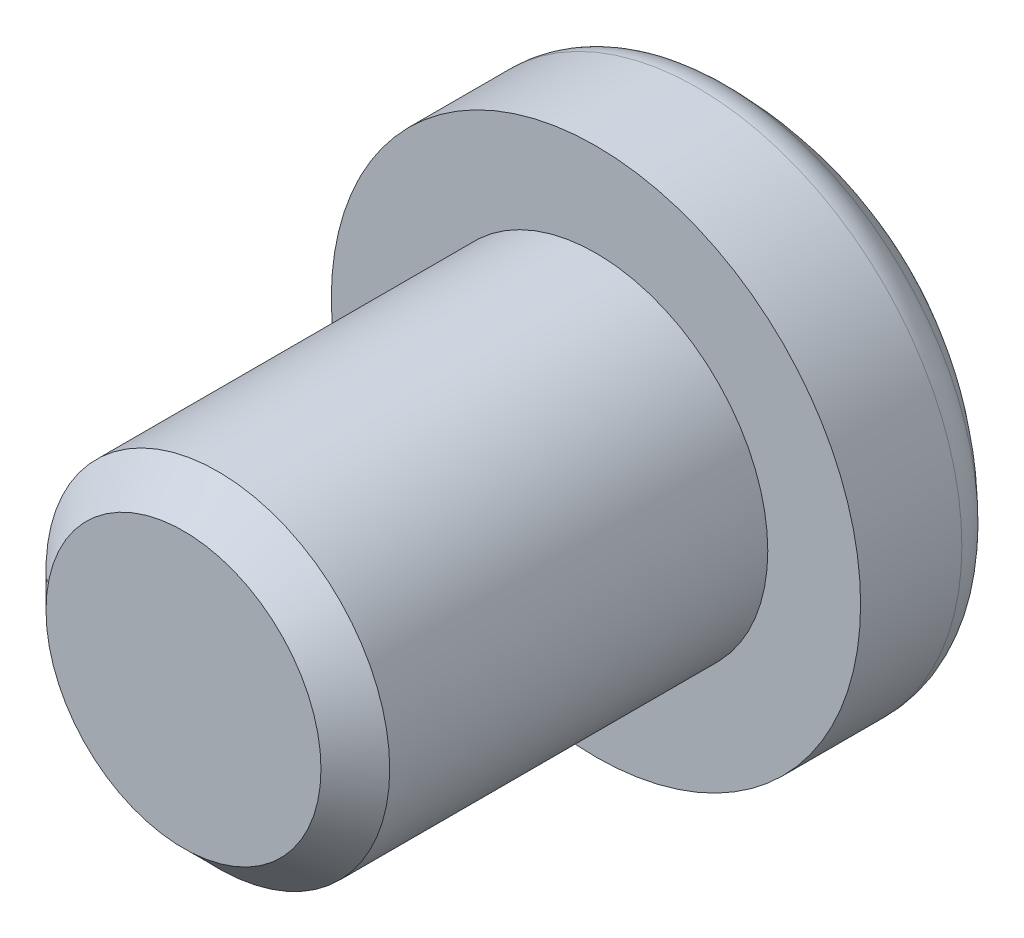
SolidWorks part; units mm, degrees
ref_plane "Plan1" through (0, 0, 0) normal (0, 0, 1) x (1, 0, 0)
ref_plane "Plan2" through (0, 0, 0) normal (0, 1, 0) x (1, 0, 0)
ref_plane "Plan3" through (0, 0, 0) normal (1, 0, 0) x (0, 0, -1)
ref_axis "Z Axis" through (0, 0, -50) along (0, 0, 1)
sketch "Esquisse1" plane through (0, 0, 0) normal (0, 1, 0) x (1, 0, 0)
  line L0 (0, 0) -> (0, 3.4) construction
  line L1 (0, 0) -> (3.85, 0)
  line L2 (0, 0) -> (0, 3.4)
  line L3 (0, 0) -> (0, 3.4) construction
  line L5 (3.85, 0) -> (3.85, 3.4) construction
  line L6 (3.85, 1.4731) -> (3.85, 0)
  arc A0 (0, 3.4) -> (3.6841, 1.8738) centre (0, -1.8096) cw
  arc A1 (3.6841, 1.8738) -> (3.85, 1.4731) centre (3.2833, 1.4731) cw
  point P9 (3.85, 1.7)
  dimension "D3" = 3.85
  dimension "D1" = 0.5667
  dimension "D2" = 3.4
revolve "Base-Révolution" add sketch "Esquisse1" angle 360 about L0 reverse direction yes
ref_plane "Plan4" through (0, 0, -3.4) normal (0, 0, 1) x (1, 0, 0)
sketch "Esquisse2" plane through (0, 0, -3.4) normal (0, 0, 1) x (1, 0, 0)
  line L0 (0.6, -0.6) -> (0.6, -2.35)
  line L1 (-2.35, 0.6) -> (-0.6, 0.6)
  line L2 (-2.35, 0.6) -> (-2.35, -0.6)
  line L3 (-2.35, -0.6) -> (-0.6, -0.6)
  line L4 (2.35, 0.6) -> (2.35, -0.6)
  line L5 (-0.6, 2.35) -> (0.6, 2.35)
  line L6 (-0.6, 2.35) -> (-0.6, 0.6)
  line L7 (-0.6, -2.35) -> (0.6, -2.35)
  line L8 (0.6, 2.35) -> (0.6, 0.6)
  line L9 (0.6, 0.6) -> (2.35, 0.6)
  line L10 (-0.6, -0.6) -> (-0.6, -2.35)
  line L11 (0.6, -0.6) -> (2.35, -0.6)
  dimension "D2" = 4.7
  dimension "D3" = 2.35
  dimension "D4" = 2.35
  dimension "D5" = 4.7
extrude "Enlev. mat.-Extru.1" cut sketch "Esquisse2" along normal blind 1.2
sketch "Esquisse3" plane through (0, 0, 0) normal (0, 1, 0) x (1, 0, 0)
  line L1 (0, 0) -> (0, -6) construction
  line L2 (0, 0) -> (2.5, 0)
  line L3 (0, 0) -> (0, -6)
  line L4 (0, -6) -> (2.5, -6)
  line L6 (2.5, 0) -> (2.5, -6)
  dimension "D1" = 6
  dimension "D2" = 2.5
revolve "Boss.-Révol.1" add sketch "Esquisse3" angle 360 about L1 reverse direction yes
sketch "Esquisse4" plane through (0, 0, 0) normal (0, 1, 0) x (1, 0, 0)
  line L0 (2.012, -6.0488) -> (2.012, -5.9512)
  line L2 (2.012, -5.9512) -> (2.5488, -5.6413)
  line L3 (2.012, -6.0488) -> (2.5488, -6.3587)
  line L4 (2.5488, -5.6413) -> (2.5488, -6.3587)
  line L6 (-2.5, -6) -> (2.5, -6) construction
  line L7 (2.5, -6) -> (2.5, 0) construction
  point P4 (2.5, -6)
  dimension "D2" = 0.0488
  dimension "D3" = 0.0488
  dimension "D4" = 0.5368
  dimension "D5" = 60
  dimension "D1" = 0.488
  dimension "D6" = 60
chamfer "Chanfrein1" distance 0.5 angle 45 1 edges at (2.5, 0, 6)
sketch "Esquisse5" plane through (0, 0, 6) normal (0, 0, 1) x (1, 0, 0)
  circle A0 centre (0, 0) radius 2.5 construction
  circle A1 centre (0, 0) radius 2.5
curve "Hélice1" pitch 0.8 height 9.68 turns 12.1
sweep "Enlèvement de matière-Balayage1" [suppressed] cut profiles "Esquisse4" path "Hélice1"
sketch "Esquisse6" plane through (0, 0, -2.2) normal (0, 0, -1) x (-1, 0, 0)
  line L12 (2.35, -0.6) -> (2.35, 0.6)
  line L13 (2.35, 0.6) -> (0.6, 0.6)
  line L14 (0.6, 0.6) -> (0.6, 2.35)
  line L15 (0.6, 2.35) -> (-0.6, 2.35)
  line L16 (-0.6, 2.35) -> (-0.6, 0.6)
  line L17 (-0.6, 0.6) -> (-2.35, 0.6)
  line L18 (-2.35, 0.6) -> (-2.35, -0.6)
  line L19 (-2.35, -0.6) -> (-0.6, -0.6)
  line L20 (-0.6, -0.6) -> (-0.6, -2.35)
  line L21 (-0.6, -2.35) -> (0.6, -2.35)
  line L22 (0.6, -2.35) -> (0.6, -0.6)
  line L23 (0.6, -0.6) -> (2.35, -0.6)
  line L24 (2.35, -0.6) -> (2.35, 0.6)
  line L25 (2.35, 0.6) -> (0.6, 0.6)
  line L26 (0.6, 0.6) -> (0.6, 2.35)
  line L27 (0.6, 2.35) -> (-0.6, 2.35)
  line L28 (-0.6, 2.35) -> (-0.6, 0.6)
  line L29 (-0.6, 0.6) -> (-2.35, 0.6)
  line L30 (-2.35, 0.6) -> (-2.35, -0.6)
  line L31 (-2.35, -0.6) -> (-0.6, -0.6)
  line L32 (-0.6, -0.6) -> (-0.6, -2.35)
  line L33 (-0.6, -2.35) -> (0.6, -2.35)
  line L34 (0.6, -2.35) -> (0.6, -0.6)
  line L35 (0.6, -0.6) -> (2.35, -0.6)
  dimension "D1" = 0
extrude "Enlèv. mat.-Extru.1" cut sketch "Esquisse6" against normal blind 2
equation "\"D1@Chanfrein1\"=\"D2@Esquisse3\"*0.2"
equation "\"D3@Esquisse4\"=0.1*\"D1@Esquisse4\""
equation "\"D4@Esquisse4\"=1.1*\"D1@Esquisse4\""
equation "\"D2@Esquisse4\"=0.1*\"D1@Esquisse4\""
equation "\"D1@Esquisse4\"=0.61*\"D4@Hélice1\""
equation "\"D1@Plan4\"=\"D2@Esquisse1\""
equation "\"D1@Esquisse1\"=\"D2@Esquisse1\"/6"
